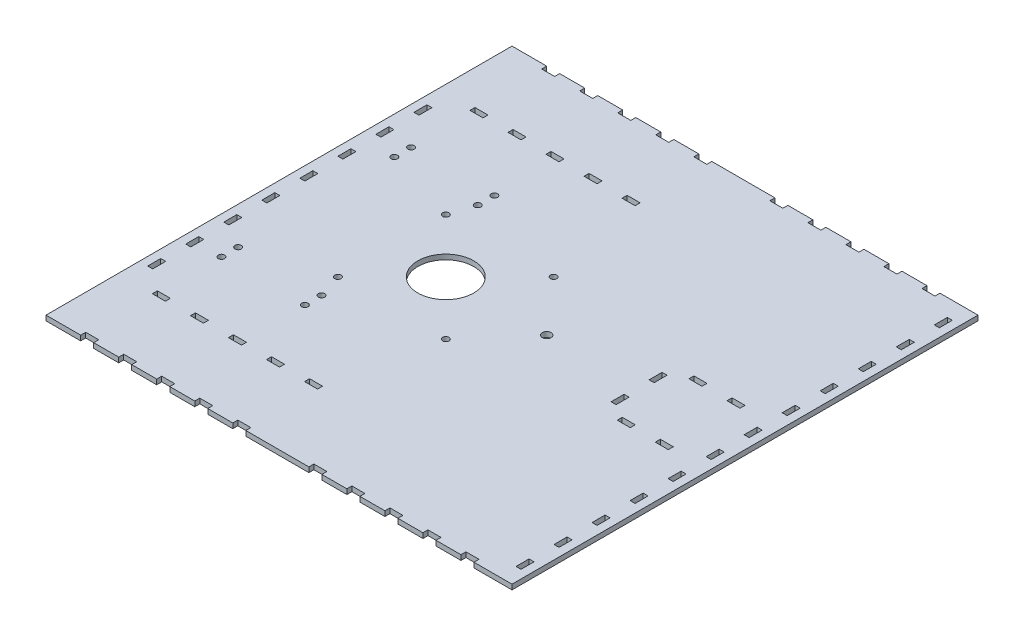
SolidWorks part; units mm, degrees
material "ENPH 253 Hardboard"
ref_plane "Front Plane" through (0, 0, 0) normal (0, 0, 1) x (1, 0, 0)
ref_plane "Top Plane" through (0, 0, 0) normal (0, 1, 0) x (1, 0, 0)
ref_plane "Right Plane" through (0, 0, 0) normal (1, 0, 0) x (0, 0, -1)
sketch "Sketch1" plane through (0, 0, 0) normal (0, 1, 0) x (1, 0, 0)
  line L0 (0, -139.7) -> (0, 139.7) construction
  line L1 (-139.7, 139.7) -> (139.7, 139.7)
  line L2 (-139.7, 139.7) -> (-139.7, -139.7)
  line L3 (-139.7, -139.7) -> (139.7, -139.7)
  line L4 (139.7, 139.7) -> (139.7, -139.7)
  line L5 (-139.7, 139.7) -> (139.7, -139.7) construction
  line L6 (-139.7, -139.7) -> (139.7, 139.7) construction
  line L12 (-139.7, 0) -> (139.7, 0) construction
  point P0 (0, 0)
  dimension "D1" = 279.4
  dimension "D2" = 279.4
extrude "Boss-Extrude1" add sketch "Sketch1" along normal blind 3
sketch "Sketch3" plane through (0, 0, 0) normal (0, -1, 0) x (-1, 0, 0)
  line L0 (-139.7, -139.7) -> (-139.7, 139.7) construction
  line L1 (-134.7, 129.3) -> (-131.7, 129.3)
  line L2 (-134.7, 129.3) -> (-134.7, 121.5)
  line L3 (-134.7, 121.5) -> (-131.7, 121.5)
  line L4 (-131.7, 129.3) -> (-131.7, 121.5)
  line L5 (-139.7, 139.7) -> (139.7, 139.7) construction
  dimension "D1" = 5
  dimension "D2" = 10.4
  dimension "D3" = 7.8
  dimension "D4" = 3
extrude "Cut-Extrude2" cut sketch "Sketch3" against normal through all
pattern_linear "LPattern1" count 12 spacing 22.8 along (0, 0, 1) of "Cut-Extrude2"
sketch "Sketch5" plane through (0, 0, 0) normal (0, -1, 0) x (1, 0, 0)
  line L0 (139.7, -139.7) -> (-139.7, -139.7) construction
  line L1 (109.1, -139.7) -> (116.9, -139.7)
  line L2 (109.1, -139.7) -> (109.1, -136.7)
  line L3 (109.1, -136.7) -> (116.9, -136.7)
  line L4 (116.9, -139.7) -> (116.9, -136.7)
  line L5 (139.7, 139.7) -> (139.7, -139.7) construction
  dimension "D1" = 22.8
  dimension "D2" = 7.8
  dimension "D3" = 3
extrude "Cut-Extrude3" cut sketch "Sketch5" against normal through all
pattern_linear "LPattern2" count 11 spacing 22.8 along (-1, 0, 0) skipping (5, 0) of "Cut-Extrude3"
mirror "Mirror2" about plane through (0, 0, 0) normal (0, 0, 1) of "LPattern2"
sketch "Sketch6" plane through (0, 0, 0) normal (0, -1, 0) x (1, 0, 0)
  line L0 (63.5, -139.7) -> (48.5, -139.7) construction
  line L1 (-134.7, -83.7) -> (-131.7, -83.7)
  line L2 (-134.7, -83.7) -> (-134.7, -75.9)
  line L3 (-134.7, -75.9) -> (-131.7, -75.9)
  line L4 (-131.7, -83.7) -> (-131.7, -75.9)
  line L5 (-139.7, -139.7) -> (-139.7, 139.7) construction
  dimension "D1" = 56
  dimension "D2" = 5
  dimension "D3" = 3
  dimension "D4" = 7.8
extrude "Cut-Extrude4" cut sketch "Sketch6" against normal through all
pattern_linear "LPattern3" count 8 spacing 22.8 along (0, 0, 1) of "Cut-Extrude4"
sketch "Sketch7" plane through (0, 0, 0) normal (0, -1, 0) x (-1, 0, 0)
  line L1 (139.7, 139.7) -> (139.7, -139.7) construction
  line L3 (-63.5, 139.7) -> (-48.5, 139.7) construction
  circle A0 centre (39.7, 0) radius 16.75
  dimension "D1" = 33.5
  dimension "D2" = 100
  dimension "D3" = 139.7
extrude "Cut-Extrude5" cut sketch "Sketch7" against normal through all
hole_wizard "#6 Clearance Hole1" positions "Sketch8" profile "Sketch9" hole size "#6" standard "ANSI Inch" end condition through all
sketch "Sketch8" plane through (0, 3, 0) normal (0, 1, 0) x (1, 0, 0)
  line L0 (-72.025, -32.325) -> (-72.025, 32.325) construction
  line L1 (-72.025, 32.325) -> (-7.375, 32.325) construction
  line L2 (-7.375, 32.325) -> (-7.375, -32.325) construction
  line L3 (-7.375, -32.325) -> (-72.025, -32.325) construction
  point P0 (-72.025, -32.325)
  point P2 (-72.025, 32.325)
  point P4 (-7.375, 32.325)
  point P6 (-7.375, -32.325)
  dimension "D1" = 64.65
  dimension "D2" = 64.65
  dimension "D3" = 90
  dimension "D4" = 64.65
  dimension "D5" = 32.325
  dimension "D6" = 32.325
sketch "Sketch9" plane through (-72.025, 3, 32.325) normal (1, 0, 0) x (0, 0, 1)
  line L0 (0, 0) -> (0, 3)
  line L1 (0, 3) -> (1.8986, 3)
  line L2 (1.8986, 3) -> (1.8986, 0)
  line L5 (1.8986, 0) -> (0, 0)
  line L11 (0, -6.35) -> (0, 107.95) construction
  dimension "Thru Hole Dia." = 3.7973
  dimension "Thru Hole Depth" = 3
hole_wizard "#6 Clearance Hole2" positions "Sketch10" profile "Sketch11" hole size "#6" standard "ANSI Inch" end condition through all
sketch "Sketch10" plane through (0, 3, 0) normal (0, 1, 0) x (1, 0, 0)
  line L1 (-118.9, 139.7) -> (-139.7, 139.7) construction
  line L2 (-139.7, -139.7) -> (-118.9, -139.7) construction
  line L3 (-73.3, 139.7) -> (-88.3, 139.7) construction
  line L4 (-88.3, -139.7) -> (-73.3, -139.7) construction
  line L5 (-139.7, 139.7) -> (-139.7, -139.7) construction
  point P0 (-117.36, 56.83)
  point P2 (-67.36, 56.83)
  point P4 (-117.36, -56.83)
  point P6 (-67.36, -56.83)
  point P22 (-67.36, -46.83)
  point P24 (-117.36, -46.83)
  point P26 (-67.36, 46.83)
  point P28 (-117.36, 46.83)
  dimension "D2" = 50
  dimension "D3" = 22.34
  dimension "D4" = 50
  dimension "D5" = 82.87
  dimension "D6" = 82.87
  dimension "D7" = 82.87
  dimension "D8" = 82.87
  dimension "D9" = 10
  dimension "D10" = 10
  dimension "D11" = 50
  dimension "D12" = 10
  dimension "D13" = 10
  dimension "D14" = 50
  dimension "D15" = 22.34
  dimension "D16" = 22.34
  dimension "D17" = 22.34
sketch "Sketch11" plane through (-117.36, 3, -56.83) normal (1, 0, 0) x (0, 0, 1)
  line L0 (0, 0) -> (0, 3)
  line L1 (0, 3) -> (1.8986, 3)
  line L2 (1.8986, 3) -> (1.8986, 0)
  line L5 (1.8986, 0) -> (0, 0)
  line L11 (0, -6.35) -> (0, 107.95) construction
  dimension "Thru Hole Dia." = 3.7973
  dimension "Thru Hole Depth" = 3
sketch "Sketch14" plane through (0, 0, 0) normal (0, -1, 0) x (-1, 0, 0)
  line L0 (139.7, 139.7) -> (139.7, -139.7) construction
  line L1 (-17.9, 139.7) -> (19.9, 139.7) construction
  circle A0 centre (-20.8, 0) radius 2.65
  dimension "D1" = 5.3
  dimension "D2" = 160.5
  dimension "D3" = 139.7
extrude "Cut-Extrude6" cut sketch "Sketch14" against normal through all
sketch "Sketch16" plane through (0, 0, 0) normal (0, -1, 0) x (1, 0, 0)
  line L0 (-139.7, -139.7) -> (-139.7, 139.7) construction
  line L1 (-118.9, 96.7) -> (-111.1, 96.7)
  line L2 (-118.9, 96.7) -> (-118.9, 93.7)
  line L3 (-118.9, 93.7) -> (-111.1, 93.7)
  line L4 (-111.1, 96.7) -> (-111.1, 93.7)
  line L7 (-111.1, 136.7) -> (-118.9, 136.7) construction
  dimension "D1" = 20.8
  dimension "D2" = 7.8
  dimension "D3" = 40
  dimension "D4" = 3
extrude "Cut-Extrude8" cut sketch "Sketch16" against normal through all
pattern_linear "LPattern5" count 5 spacing 22.8 along (1, 0, 0) of "Cut-Extrude8"
mirror "Mirror4" about plane through (0, 0, 0) normal (0, 0, 1) of "LPattern5"
sketch "Sketch17" plane through (0, 0, 0) normal (0, -1, 0) x (1, 0, 0)
  line L1 (116.7, 23) -> (108.9, 23)
  line L2 (116.7, 23) -> (116.7, 20)
  line L3 (116.7, 20) -> (108.9, 20)
  line L4 (108.9, 23) -> (108.9, 20)
  line L5 (94.1, 139.7) -> (109.1, 139.7) construction
  line L6 (139.7, 139.7) -> (139.7, -139.7) construction
  point P8 (116.7, 21.5)
  dimension "D1" = 116.7
  dimension "D2" = 23
  dimension "D3" = 7.8
  dimension "D4" = 3
extrude "Cut-Extrude9" cut sketch "Sketch17" against normal through all
pattern_linear "LPattern6" count 2 spacing 22.8 along (-1, 0, 0) of "Cut-Extrude9"
sketch "Sketch18" plane through (0, 0, 0) normal (0, -1, 0) x (-1, 0, 0)
  line L0 (-139.7, -139.7) -> (-139.7, 139.7) construction
  line L1 (-77.7, -15.3) -> (-74.7, -15.3)
  line L2 (-77.7, -15.3) -> (-77.7, -7.5)
  line L3 (-77.7, -7.5) -> (-74.7, -7.5)
  line L4 (-74.7, -15.3) -> (-74.7, -7.5)
  line L5 (-71.3, -139.7) -> (-86.3, -139.7) construction
  dimension "D1" = 7.8
  dimension "D2" = 3
  dimension "D3" = 62
  dimension "D4" = 124.4
extrude "Cut-Extrude10" cut sketch "Sketch18" against normal through all
mirror "Mirror5" about plane through (0, 0, 0) normal (0, 0, 1) of "Cut-Extrude10", "LPattern6", "Cut-Extrude9"
